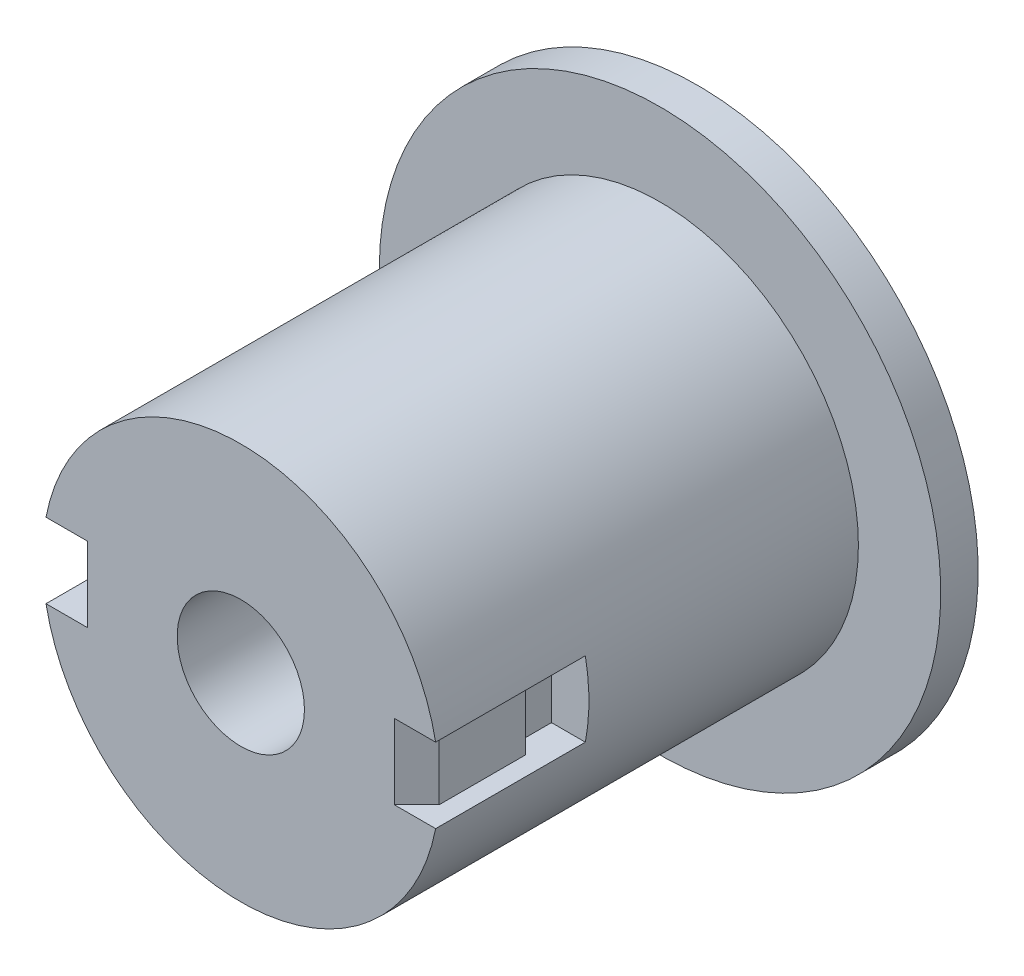
SolidWorks part; units mm, degrees
ref_plane "Front" through (0, 0, 0) normal (0, 0, 1) x (1, 0, 0)
ref_plane "Top" through (0, 0, 0) normal (0, 1, 0) x (1, 0, 0)
ref_plane "Right" through (0, 0, 0) normal (1, 0, 0) x (0, 0, -1)
sketch "Sketch1" plane through (0, 0, 0) normal (0, 0, 1) x (1, 0, 0)
  circle A0 centre (0, 0) radius 26.5
  dimension "D1" = 53
extrude "Boss-Extrude1" add sketch "Sketch1" along normal blind 56
sketch "Sketch4" plane through (0, 0, 0) normal (0, 0, -1) x (-1, 0, 0)
  circle A0 centre (0, 0) radius 37.5
  dimension "D1" = 75
extrude "Boss-Extrude2" add sketch "Sketch4" along normal blind 5
sketch "Sketch5" plane through (0, 0, 56) normal (0, 0, 1) x (1, 0, 0)
  circle A0 centre (0, 0) radius 8.5
  dimension "D1" = 17
extrude "Cut-Extrude1" cut sketch "Sketch5" against normal through all
sketch "Sketch6" plane through (0, 0, 0) normal (0, 1, 0) x (1, 0, 0)
  line L0 (23.5, -56) -> (26.5, -56)
  line L1 (26.5, -56) -> (26.5, -36)
  line L2 (26.5, -56) -> (26.5, 0) construction
  line L3 (26.5, -36) -> (21.5, -36)
  line L4 (21.5, -36) -> (21.5, -39.5)
  line L5 (21.5, -39.5) -> (23.5, -41.5)
  line L6 (23.5, -41.5) -> (23.5, -53)
  line L7 (23.5, -53) -> (20.5, -56)
  line L8 (20.5, -56) -> (23.5, -56)
  dimension "D1" = 3
  dimension "D2" = 3
  dimension "D3" = 5
  dimension "D4" = 20
  dimension "D5" = 3.5
  dimension "D6" = 3
  dimension "D7" = 135
  dimension "D8" = 135
extrude "Cut-Extrude2" cut sketch "Sketch6" against normal blind 5 and the other way blind 5
mirror "Mirror1" about plane through (0, 0, 0) normal (1, 0, 0) of "Cut-Extrude2"
